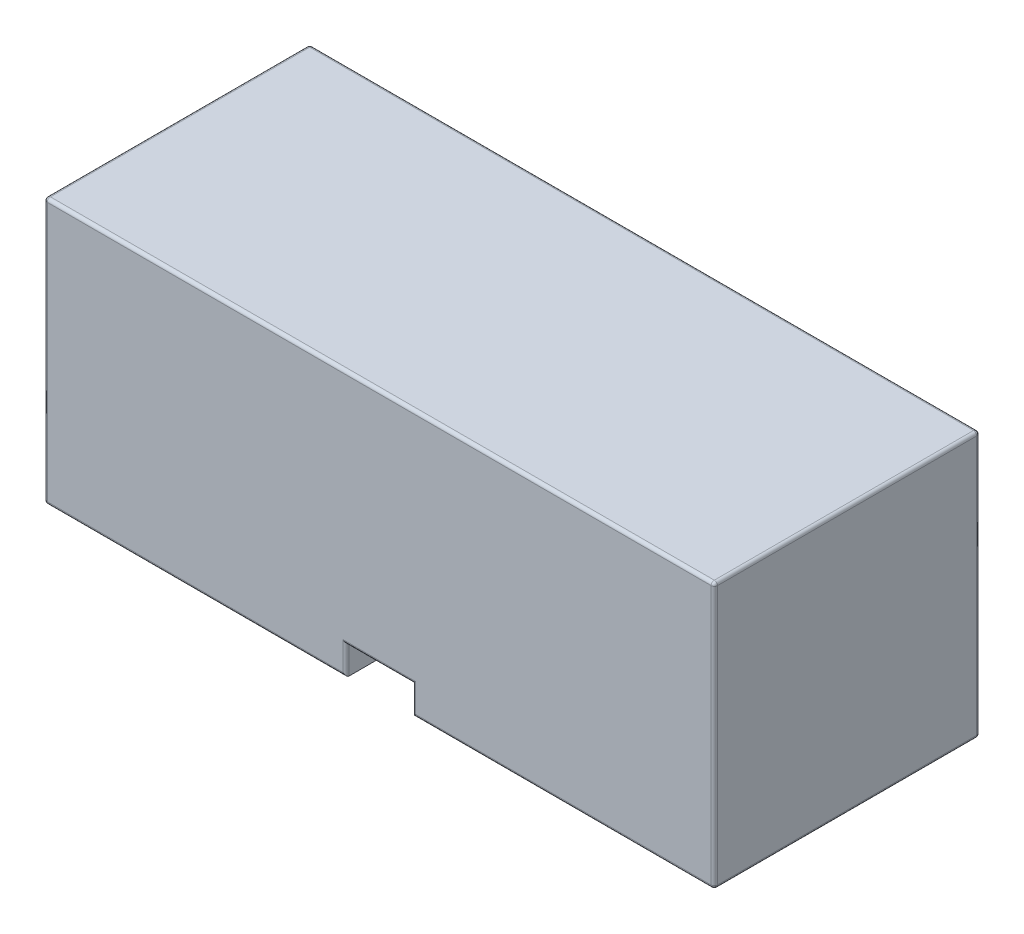
SolidWorks part; units mm, degrees
ref_plane "Plan de face" through (0, 0, 0) normal (0, 0, 1) x (1, 0, 0)
ref_plane "Plan de dessus" through (0, 0, 0) normal (0, 1, 0) x (1, 0, 0)
ref_plane "Plan de droite" through (0, 0, 0) normal (1, 0, 0) x (0, 0, -1)
sketch "Esquisse1" plane through (0, 0, 0) normal (0, 0, 1) x (1, 0, 0)
  line L1 (0, 0) -> (106, 0)
  line L2 (0, 0) -> (0, -42)
  line L3 (0, -42) -> (106, -42)
  line L4 (106, 0) -> (106, -42)
  dimension "D1" = 106
  dimension "D2" = 42
extrude "Boss.-Extru.1" add sketch "Esquisse1" along normal blind 42
sketch "Esquisse2" plane through (0, -42, 0) normal (0, -1, 0) x (1, 0, 0)
  line L0 (106, 42) -> (106, 0) construction
  line L1 (47.75, 45) -> (58.25, 45)
  line L2 (47.75, 45) -> (47.75, 34.5)
  line L3 (47.75, 34.5) -> (58.25, 34.5)
  line L4 (58.25, 45) -> (58.25, 34.5)
  line L5 (0, 42) -> (106, 42) construction
  line L13 (63.5, 26.25) -> (74, 26.25)
  line L14 (63.5, 26.25) -> (63.5, 15.75)
  line L15 (63.5, 15.75) -> (74, 15.75)
  line L16 (74, 26.25) -> (74, 15.75)
  point P4 (74, 21)
  point P7 (106, 21)
  point P8 (53, 45)
  point P11 (53, 42)
  dimension "D1" = 10.5
  dimension "D2" = 10.5
  dimension "D3" = 10.5
  dimension "D4" = 10.5
  dimension "D5" = 0
  dimension "D6" = 0
  dimension "D7" = 13.5
  dimension "D8" = 10.5
extrude "Enlèv. mat.-Extru.1" cut sketch "Esquisse2" against normal blind 4.5
ref_plane "Plan1" through (0, 0, 21) normal (0, 0, 1) x (1, 0, 0)
ref_plane "Plan2" through (53, 0, 0) normal (1, 0, 0) x (0, 0, -1)
ref_plane "Plan3" through (37, 0, 37) normal (0.7071, 0, 0.7071) x (0.7071, 0, -0.7071)
fillet "Congé1" radius 0.5 16 edges at (0, -42, 21) (82.125, -42, 42) (23.875, -42, 42) (0, -21, 42) (106, -42, 21) (106, -21, 42) (53, -42, 0) (106, -21, 0) (0, -21, 0) (106, 0, 21) (53, 0, 42) (0, 0, 21) (53, 0, 0) (58.25, -39.75, 42) (53, -37.5, 42) (47.75, -39.75, 42)
mirror "Symétrie1" about plane through (53, 0, 0) normal (1, 0, 0) of "Enlèv. mat.-Extru.1"
mirror "Symétrie2" about plane through (0, 0, 21) normal (0, 0, 1) of "Symétrie1"
